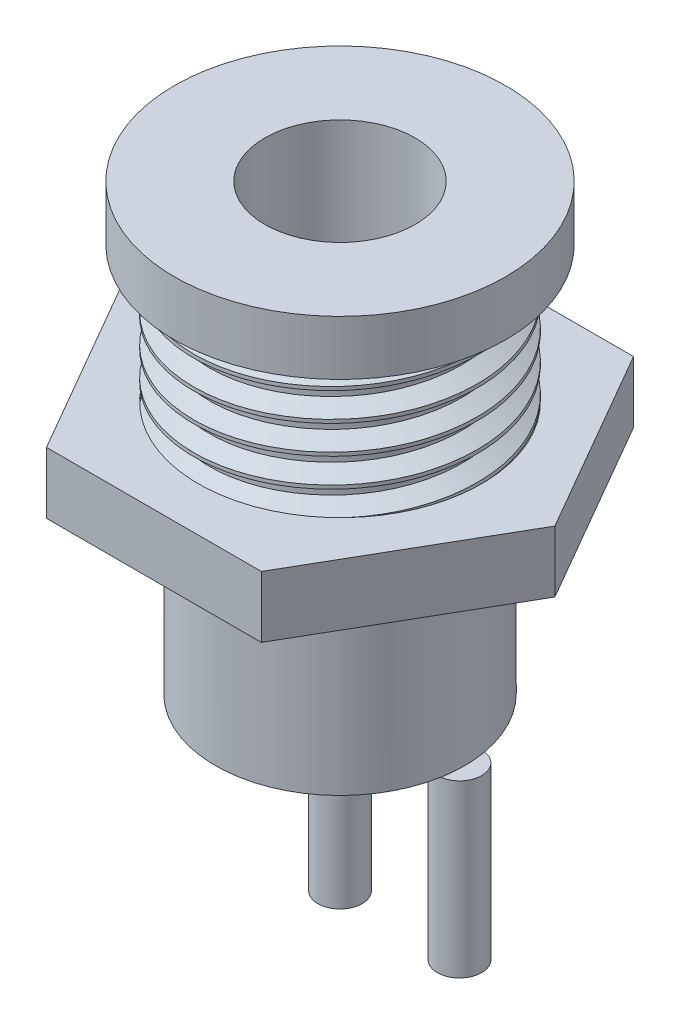
SolidWorks part; units mm, degrees
material "Plain Carbon Steel"
ref_plane "Front Plane" through (0, 0, 0) normal (0, 0, 1) x (1, 0, 0)
ref_plane "Top Plane" through (0, 0, 0) normal (0, 1, 0) x (1, 0, 0)
ref_plane "Right Plane" through (0, 0, 0) normal (1, 0, 0) x (0, 0, -1)
sketch "Sketch1" plane through (0, 0, 0) normal (0, 0, 1) x (1, 0, 0)
  line L0 (0, 0) -> (0, -37.4751) construction
  line L1 (-2.794, 0) -> (-6.1595, 0)
  line L3 (-5.2705, -2.032) -> (-6.1595, -2.032)
  line L4 (-6.1595, 0) -> (-6.1595, -2.032)
  line L6 (-5.2705, -2.032) -> (-5.2705, -16.51)
  line L7 (-5.2705, -16.51) -> (0, -16.51)
  line L8 (0, -11.938) -> (0, -16.51)
  line L10 (0, -55) -> (0, 55) construction
  line L11 (55, 0) -> (-55, 0) construction
  line L14 (0, -11.938) -> (-2.794, -11.938)
  line L15 (-2.794, 0) -> (-2.794, -11.938)
  dimension "D1" = 10.541
  dimension "D2" = 12.319
  dimension "D3" = 2.032
  dimension "D4" = 16.51
  dimension "D5" = 5.588
  dimension "D6" = 11.938
revolve "Revolve1" add sketch "Sketch1" angle 360 about L0
thread "Thread1" pitch 1.0583 method cut profile "Thread Profile1" start angle 0, offset 0, length 0, pitch 1.0583, diameter 10.541
ref_plane "Plane1" through (5.2705, -16.51, 0) normal (0, 0, 1) x (1, 0, 0)
sketch "Thread Profile1" plane through (5.2705, -16.51, 0) normal (0, 0, 1) x (1, 0, 0)
  line L0 (0, 0) -> (0, 1.0583) construction
  line L11 (0, 0) -> (0, 0.926)
  line L12 (0, 0.926) -> (-0.5728, 0.5953)
  line L13 (-0.5728, 0.5953) -> (-0.5728, 0.3307)
  line L15 (-0.5728, 0.3307) -> (0, 0)
  line L17 (-0.5728, 0.463) -> (0, 0.463) construction
  point P2 (0, 0)
  dimension "Pitch" = 1.0583
  dimension "Profile_Angle" = 60
  dimension "Profile_Land" = 0.2646
  dimension "Profile_Height" = 0.5728
sketch "Sketch8" plane through (0, -2.032, 0) normal (0, -1, 0) x (1, 0, 0)
  circle A0 centre (0, 0) radius 6.1595
  circle A1 centre (0, 0) radius 2.794 construction
  circle A2 centre (0, 0) radius 2.794
extrude "Boss-Extrude3" add sketch "Sketch8" against normal up to surface (2.032 mm away) up to face at (-6.1595, 0, 0)
sketch "Sketch9" plane through (0, -16.51, 0) normal (0, -1, 0) x (1, 0, 0)
  circle A0 centre (0, 0) radius 4.6355
  dimension "D1" = 9.271
extrude "Cut-Extrude1" cut sketch "Sketch9" against normal blind 6.35 flip side to cut
sketch "Sketch2" plane through (0, -2.032, 0) normal (0, -1, 0) x (1, 0, 0)
  line L1 (7.9923, 0) -> (3.9961, 6.9215)
  line L2 (3.9961, 6.9215) -> (-3.9961, 6.9215)
  line L3 (-3.9961, 6.9215) -> (-7.9923, 0)
  line L4 (-7.9923, 0) -> (-3.9961, -6.9215)
  line L5 (-3.9961, -6.9215) -> (3.9961, -6.9215)
  line L6 (3.9961, -6.9215) -> (7.9923, 0)
  circle A0 centre (0, 0) radius 6.9215 construction
  circle A1 centre (0, 0) radius 5.2705 construction
  circle A2 centre (0, 0) radius 5.2705
  dimension "D1" = 13.843
extrude "Boss-Extrude1" add sketch "Sketch2" along normal blind 2.286 from offset 5.08
sketch "Sketch3" plane through (0, -16.51, 0) normal (0, -1, 0) x (1, 0, 0)
  circle A0 centre (0, 0) radius 0.8255
  circle A1 centre (4.445, 0) radius 0.8255
  circle A3 centre (0, 0) radius 5.2705 construction
  dimension "D1" = 1.651
extrude "Boss-Extrude2" add sketch "Sketch3" along normal blind 6.35
